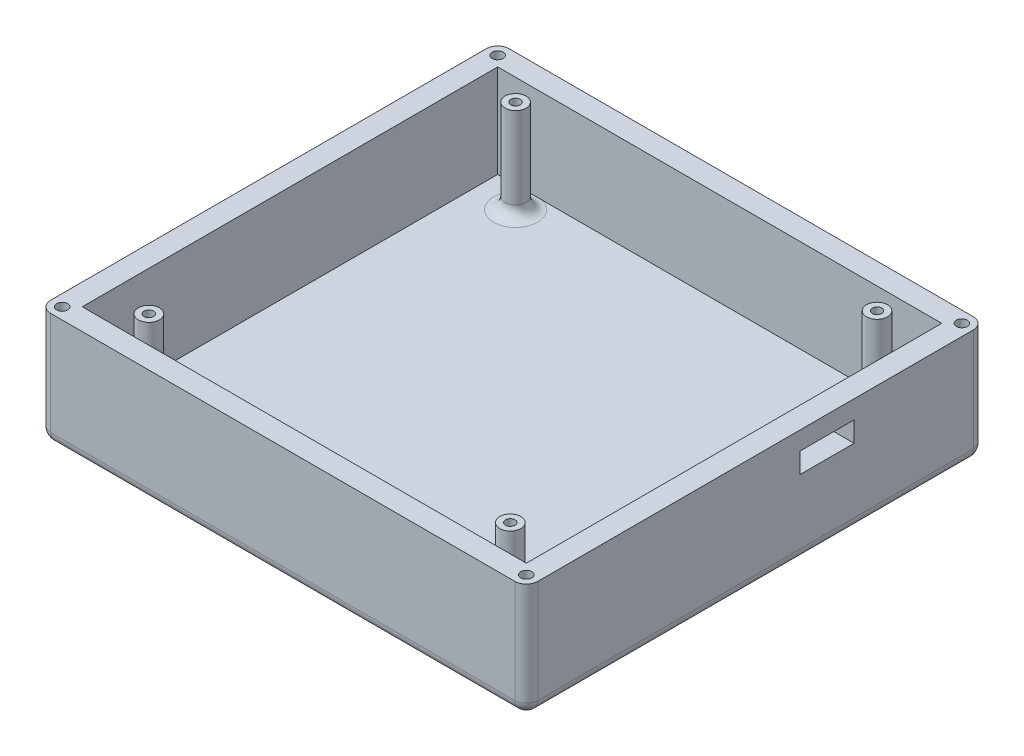
SolidWorks part; units mm, degrees
ref_plane "Front Plane" through (0, 0, 0) normal (0, 0, 1) x (1, 0, 0)
ref_plane "Top Plane" through (0, 0, 0) normal (0, 1, 0) x (1, 0, 0)
ref_plane "Right Plane" through (0, 0, 0) normal (1, 0, 0) x (0, 0, -1)
sketch "Sketch1" plane through (0, 0, 0) normal (0, 0, 1) x (1, 0, 0)
  line L1 (-53.975, 25.4) -> (53.975, 25.4)
  line L2 (-53.975, 25.4) -> (-53.975, 0)
  line L3 (-53.975, 0) -> (53.975, 0)
  line L4 (53.975, 25.4) -> (53.975, 0)
  point P4 (0, 0)
  dimension "D1" = 25.4
  dimension "D2" = 107.95
extrude "Boss-Extrude1" add sketch "Sketch1" along normal mid plane 101.6
sketch "Sketch2" plane through (0, 25.4, 0) normal (0, 1, 0) x (1, 0, 0)
  line L0 (53.975, 50.8) -> (-53.975, 50.8) construction
  line L1 (-49.2125, -46.0375) -> (49.2125, -46.0375)
  line L2 (-49.2125, -46.0375) -> (-49.2125, 46.0375)
  line L3 (-49.2125, 46.0375) -> (49.2125, 46.0375)
  line L4 (49.2125, -46.0375) -> (49.2125, 46.0375)
  line L5 (-49.2125, -46.0375) -> (49.2125, 46.0375) construction
  line L6 (-49.2125, 46.0375) -> (49.2125, -46.0375) construction
  line L7 (53.975, -50.8) -> (53.975, 50.8) construction
  point P0 (0, 0)
  dimension "D1" = 4.7625
  dimension "D2" = 4.7625
extrude "Cut-Extrude1" cut sketch "Sketch2" against normal offset from surface (20.6375 mm away) 4.7625 up to face at (0, 0, 0)
fillet "Fillet1" radius 2.54 4 edges at (53.975, 12.7, -50.8) (-53.975, 12.7, -50.8) (-53.975, 12.7, 50.8) (53.975, 12.7, 50.8)
sketch "Sketch6" plane through (0, 4.7625, 0) normal (0, 1, 0) x (1, 0, 0)
  line L0 (111.7366, 286.9927) -> (745.2477, 153.2391) construction
sketch "Sketch7" plane through (0, 4.7625, 0) normal (0, 1, 0) x (1, 0, 0)
  line L0 (255.5407, 500.0952) -> (944.874, 500.0952) construction
  line L1 (132.6927, 535.169) -> (847.3593, 535.169) construction
fillet "Fillet2" radius 2.54 8 edges at (-53.2311, 0, 50.0561) (0, 0, 50.8) (53.2311, 0, 50.0561) (53.975, 0, 0) (53.2311, 0, -50.0561) (0, 0, -50.8) (-53.2311, 0, -50.0561) (-53.975, 0, 0)
sketch "Sketch8" plane through (0, 25.4, 0) normal (0, 1, 0) x (1, 0, 0)
  circle A0 centre (-51.435, -48.26) radius 1.2192
  circle A1 centre (51.435, -48.26) radius 1.2192
  circle A2 centre (-51.435, 48.26) radius 1.2192
  circle A3 centre (51.435, 48.26) radius 1.2192
extrude "Cut-Extrude2" cut sketch "Sketch8" against normal blind 5.08
sketch "Sketch9" plane through (0, 4.7625, 0) normal (0, 1, 0) x (1, 0, 0)
  circle A0 centre (-40.4792, 41.2715) radius 1.0525
  circle A1 centre (-40.4792, 41.2715) radius 2.3225
  dimension "D1" = 1.27
extrude "Boss-Extrude2" add sketch "Sketch9" along normal up to surface (20.6375 mm away) up to face at (50.2158, 25.4, 48.26)
pattern_linear "LPattern1" count 2 spacing 80.1116 along (1, 0, 0) count 2 spacing 81.28 along (0, 0, 1) of "Boss-Extrude2"
sketch "Sketch10" plane through (53.975, 0, 0) normal (1, 0, 0) x (0, 0, -1)
  line L1 (9.8495, 21.3516) -> (21.8495, 21.3516)
  line L2 (9.8495, 21.3516) -> (9.8495, 16.8516)
  line L3 (9.8495, 16.8516) -> (21.8495, 16.8516)
  line L4 (21.8495, 21.3516) -> (21.8495, 16.8516)
  dimension "D1" = 12
  dimension "D2" = 4.5
extrude "Cut-Extrude3" cut sketch "Sketch10" against normal up to surface (4.7625 mm away) up to face at (49.2125, 15.0813, 0)
fillet "Fillet3" radius 2.54 4 edges at (-40.4792, 4.7625, 42.331) (39.6324, 4.7625, 42.331) (39.6324, 4.7625, -38.949) (-40.4792, 4.7625, -38.949)
